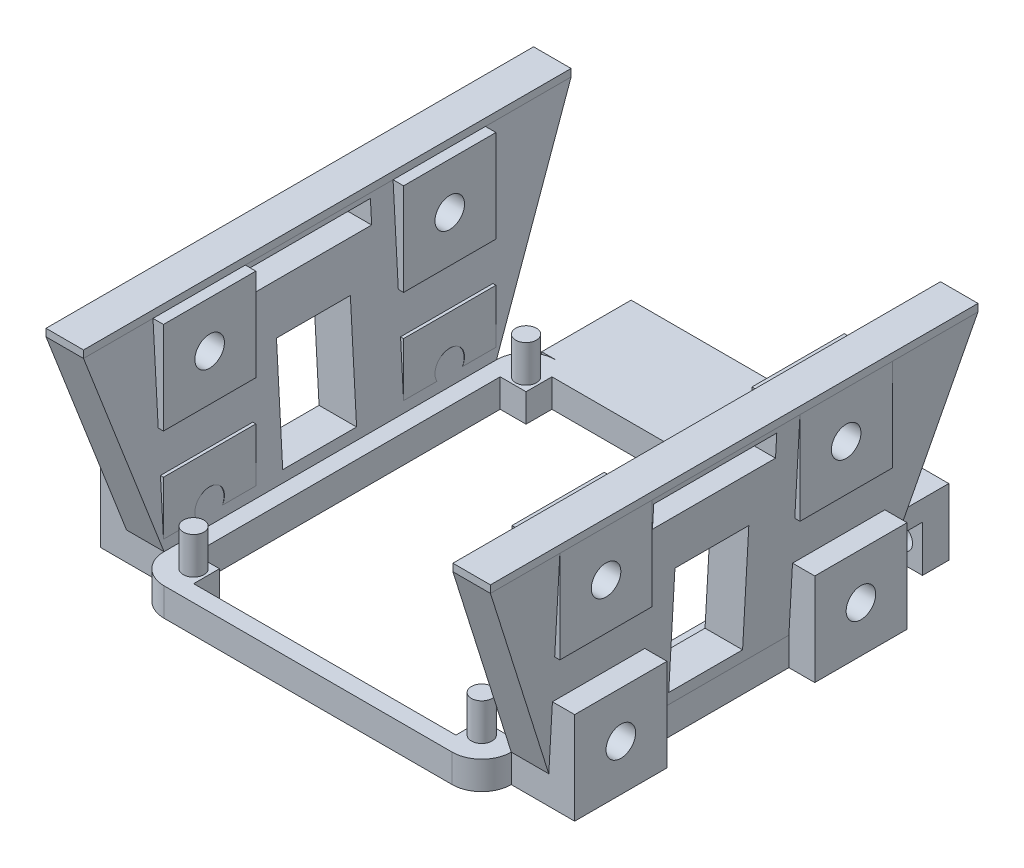
SolidWorks part; units mm, degrees
ref_plane "Front Plane" through (0, 0, 0) normal (0, 0, 1) x (1, 0, 0)
ref_plane "Top Plane" through (0, 0, 0) normal (0, 1, 0) x (1, 0, 0)
ref_plane "Right Plane" through (0, 0, 0) normal (1, 0, 0) x (0, 0, -1)
sketch "Sketch1" plane through (0, 836.5359, 0) normal (0, -1, 0) x (1, 0, 0)
  line L0 (675.181, 1276.1699) -> (675.181, 1329.1699) construction
  line L1 (655.681, 1276.1699) -> (694.6809, 1276.1699) construction
  line L2 (694.681, 1329.1699) -> (655.681, 1329.1699) construction
  line L4 (655.6809, 1276.1699) -> (694.681, 1276.1699)
  line L5 (651.6809, 1280.1699) -> (651.6809, 1325.1699)
  line L6 (655.6809, 1329.1699) -> (694.681, 1329.1699)
  line L7 (698.681, 1280.1699) -> (698.681, 1325.1699)
  line L8 (651.6809, 1276.1699) -> (698.681, 1329.1699) construction
  line L9 (651.6809, 1329.1699) -> (698.681, 1276.1699) construction
  arc A0 (651.6809, 1325.1699) -> (655.6809, 1329.1699) centre (655.6809, 1325.1699) cw
  arc A1 (655.6809, 1276.1699) -> (651.6809, 1280.1699) centre (655.6809, 1280.1699) cw
  arc A2 (694.681, 1276.1699) -> (698.681, 1280.1699) centre (694.681, 1280.1699) ccw
  arc A3 (694.681, 1329.1699) -> (698.681, 1325.1699) centre (694.681, 1325.1699) cw
  point P6 (675.181, 1302.6699)
  dimension "D3" = 4
  dimension "D1" = 53
  dimension "D2" = 47
extrude "Boss-Extrude1" add sketch "Sketch1" along normal blind 3.81
sketch "Sketch2" plane through (0, 836.5359, 0) normal (0, 1, 0) x (1, 0, 0)
  line L0 (651.6809, -1280.1699) -> (651.6809, -1325.1699) construction
  line L1 (694.6809, -1276.1699) -> (655.681, -1276.1699) construction
  line L2 (698.681, -1280.1699) -> (698.681, -1325.1699) construction
  circle A0 centre (655.6809, -1280.1699) radius 1.4
  circle A1 centre (694.6809, -1280.1699) radius 1.4
  circle A2 centre (694.681, -1325.1699) radius 1.4
  circle A3 centre (655.681, -1325.1699) radius 1.4
  dimension "D1" = 2.8
  dimension "D2" = 39
  dimension "D3" = 45
  dimension "D4" = 4
  dimension "D5" = 4
  dimension "D6" = 45
  dimension "D7" = 39
  dimension "D8" = 4
  dimension "D9" = 4
sketch "Sketch4" plane through (0, 868.1359, 0) normal (0, -1, 0) x (1, 0, 0)
  line L1 (652.181, 1336.5723) -> (698.181, 1336.5723)
  line L2 (650.181, 1334.5723) -> (650.181, 1268.5723)
  line L3 (652.181, 1266.5723) -> (698.181, 1266.5723)
  line L4 (700.181, 1334.5723) -> (700.181, 1268.5723)
  line L5 (650.181, 1336.5723) -> (700.181, 1266.5723) construction
  line L6 (650.181, 1266.5723) -> (700.181, 1336.5723) construction
  arc A0 (650.181, 1268.5723) -> (652.181, 1266.5723) centre (652.181, 1268.5723) ccw
  arc A1 (698.181, 1266.5723) -> (700.181, 1268.5723) centre (698.181, 1268.5723) ccw
  arc A2 (698.181, 1336.5723) -> (700.181, 1334.5723) centre (698.181, 1334.5723) cw
  arc A3 (652.181, 1336.5723) -> (650.181, 1334.5723) centre (652.181, 1334.5723) ccw
  point P4 (675.181, 1301.5723)
  dimension "D1" = 2
extrude "Boss-Extrude4" add sketch "Sketch4" along normal blind 5 separate body
ref_plane "Plane1" through (0, 0, 1302.6699) normal (0, 0, 1) x (1, 0, 0)
extrude "Boss-Extrude5" add sketch "Sketch2" along normal blind 5
sketch "Sketch6" plane through (0, 832.7259, 0) normal (0, -1, 0) x (1, 0, 0)
  line L0 (675.181, 1329.1699) -> (675.181, 1276.1699) construction
  line L1 (694.681, 1329.1699) -> (655.6809, 1329.1699) construction
  line L2 (655.6809, 1276.1699) -> (694.681, 1276.1699) construction
sketch "Sketch8" plane through (0, 868.1359, 0) normal (0, 1, 0) x (1, 0, 0)
  line L0 (650.181, -1268.5723) -> (650.181, -1334.5723)
  line L1 (650.181, -1268.5723) -> (645.101, -1268.5723)
  line L2 (650.181, -1334.5723) -> (645.101, -1334.5723)
  line L3 (645.101, -1268.5723) -> (645.101, -1334.5723)
  line L4 (652.181, -1266.5723) -> (698.181, -1266.5723)
  line L5 (652.181, -1266.5723) -> (652.181, -1261.4923)
  line L6 (698.181, -1266.5723) -> (698.181, -1261.4923)
  line L7 (652.181, -1261.4923) -> (698.181, -1261.4923)
  line L8 (650.181, -1301.5723) -> (700.181, -1301.5723) construction
  line L9 (700.181, -1268.5723) -> (700.181, -1334.5723) construction
  line L10 (652.181, -1341.6523) -> (698.181, -1341.6523)
  line L11 (698.181, -1336.5723) -> (698.181, -1341.6523)
  line L12 (652.181, -1336.5723) -> (652.181, -1341.6523)
  line L13 (652.181, -1336.5723) -> (698.181, -1336.5723)
  line L14 (675.181, -1329.1699) -> (675.181, -1276.1699) construction
  line L15 (705.2609, -1268.5723) -> (705.2609, -1334.5723)
  line L16 (700.1809, -1334.5723) -> (705.2609, -1334.5723)
  line L17 (700.1809, -1268.5723) -> (705.2609, -1268.5723)
  line L18 (700.1809, -1268.5723) -> (700.1809, -1334.5723)
  dimension "D1" = 5.08
extrude "Boss-Extrude7" add sketch "Sketch8" against normal up to surface (5 mm away) separate body up to face at (675.181, 863.1359, 1301.5723)
sketch "Sketch10" plane through (0, 832.7259, 0) normal (0, -1, 0) x (1, 0, 0)
  line L0 (651.6809, 1325.1699) -> (651.6809, 1280.1699)
  line L1 (651.6809, 1325.1699) -> (646.6009, 1325.1699)
  line L2 (651.6809, 1280.1699) -> (646.6009, 1280.1699)
  line L3 (646.6009, 1325.1699) -> (646.6009, 1280.1699)
  line L8 (698.681, 1325.1699) -> (698.681, 1280.1699)
  line L9 (698.681, 1325.1699) -> (703.761, 1325.1699)
  line L10 (698.681, 1280.1699) -> (703.761, 1280.1699)
  line L11 (703.761, 1325.1699) -> (703.761, 1280.1699)
  dimension "D1" = 5.08
extrude "Boss-Extrude8" add sketch "Sketch10" against normal up to surface (3.81 mm away) separate body up to face at (654.281, 836.5359, 1325.1699)
loft "Loft6" add section face at (649.1409, 836.5359, 1302.6699) section face at (647.641, 863.1359, 1301.5723) connector at (646.6009, 836.5359, 1325.1699) connector at (645.101, 863.1359, 1334.5723)
loft "Loft8" add section face at (702.7209, 863.1359, 1301.5723) section face at (701.221, 836.5359, 1302.6699) start constraint default connector at (700.1809, 863.1359, 1334.5723) connector at (698.681, 836.5359, 1325.1699)
sketch "Sketch12" plane through (0, 0, 1341.6523) normal (0, 0, 1) x (1, 0, 0)
  line L1 (645.101, 868.1359) -> (705.2609, 868.1359)
  line L2 (645.101, 868.1359) -> (645.101, 863.1359)
  line L3 (645.101, 863.1359) -> (705.2609, 863.1359)
  line L4 (705.2609, 868.1359) -> (705.2609, 863.1359)
  line L5 (645.101, 868.1359) -> (705.2609, 863.1359) construction
  line L6 (645.101, 863.1359) -> (705.2609, 868.1359) construction
  point P4 (675.181, 865.6359)
extrude "Cut-Extrude1" cut sketch "Sketch12" against normal through all
sketch "Sketch13" plane through (0, 836.5359, 0) normal (0, 1, 0) x (1, 0, 0)
  line L0 (675.181, -1329.1699) -> (675.181, -1276.1699) construction
  line L1 (657.431, -1326.9199) -> (692.931, -1326.9199)
  line L2 (653.931, -1323.4199) -> (653.931, -1281.9199)
  line L3 (657.431, -1278.4199) -> (692.931, -1278.4199)
  line L4 (696.431, -1323.4199) -> (696.431, -1281.9199)
  line L5 (653.931, -1326.9199) -> (696.431, -1278.4199) construction
  line L6 (653.931, -1278.4199) -> (696.431, -1326.9199) construction
  line L7 (675.181, -1278.4199) -> (675.181, -1326.9199) construction
  line L10 (653.931, -1281.9199) -> (657.431, -1281.9199)
  line L11 (657.431, -1278.4199) -> (657.431, -1281.9199)
  line L12 (653.931, -1278.4199) -> (657.431, -1281.9199) construction
  line L13 (653.931, -1281.9199) -> (657.431, -1278.4199) construction
  line L14 (-2.0955, -1302.6699) -> (2.0955, -1302.6699) construction
  line L15 (653.931, -1323.4199) -> (657.431, -1326.9199) construction
  line L16 (653.931, -1326.9199) -> (657.431, -1323.4199) construction
  line L17 (657.431, -1326.9199) -> (657.431, -1323.4199)
  line L18 (653.931, -1323.4199) -> (657.431, -1323.4199)
  line L21 (696.431, -1326.9199) -> (692.931, -1323.4199) construction
  line L22 (696.431, -1323.4199) -> (692.931, -1326.9199) construction
  line L25 (696.431, -1323.4199) -> (692.931, -1323.4199)
  line L26 (692.931, -1326.9199) -> (692.931, -1323.4199)
  line L27 (696.431, -1281.9199) -> (692.931, -1278.4199) construction
  line L28 (696.431, -1278.4199) -> (692.931, -1281.9199) construction
  line L29 (692.931, -1278.4199) -> (692.931, -1281.9199)
  line L30 (696.431, -1281.9199) -> (692.931, -1281.9199)
  point P0 (675.181, -1302.6699)
  point P10 (655.681, -1280.1699)
  point P18 (655.681, -1325.1699)
  point P22 (694.681, -1325.1699)
  point P26 (694.681, -1280.1699)
  dimension "D1" = 48.5
  dimension "D2" = 42.5
  dimension "D3" = 3.5
  dimension "D4" = 3.5
extrude "Cut-Extrude2" cut sketch "Sketch13" against normal through all
ref_plane "Plane2" through (675.181, 0, 0) normal (1, 0, 0) x (0, 0, -1)
sketch "Sketch14" plane through (675.181, 0, 0) normal (1, 0, 0) x (0, 0, -1)
  line L0 (-1304.1057, 838.1559) -> (-1304.1057, 853.1559) construction
  line L1 (-1304.1057, 853.1559) -> (-1304.1057, 863.1359) construction
  line L2 (-1309.0256, 838.0359) -> (-1299.0256, 838.0359)
  line L3 (-1309.0256, 838.0359) -> (-1309.0256, 853.0359)
  line L4 (-1309.0256, 853.0359) -> (-1299.0256, 853.0359)
  line L5 (-1299.0256, 838.0359) -> (-1299.0256, 853.0359)
  line L6 (-1309.0256, 838.0359) -> (-1299.0256, 853.0359) construction
  line L7 (-1309.0256, 853.0359) -> (-1299.0256, 838.0359) construction
  line L8 (-1325.1699, 836.5359) -> (-1280.1699, 836.5359) construction
  line L9 (-1325.1699, 836.5359) -> (-1325.1699, 832.7259) construction
  line L10 (-1325.1699, 832.7259) -> (-1280.1699, 832.7259) construction
  line L11 (-1280.1699, 836.5359) -> (-1280.1699, 832.7259) construction
  line L12 (-1325.1699, 836.5359) -> (-1280.1699, 832.7259) construction
  line L13 (-1325.1699, 832.7259) -> (-1280.1699, 836.5359) construction
  line L18 (-1295.7772, 859.486) -> (-1312.4342, 859.486)
  line L19 (-1295.7772, 859.486) -> (-1295.7772, 862.5199)
  line L20 (-1312.4342, 859.486) -> (-1312.4342, 862.5199)
  line L21 (-1295.7772, 862.5199) -> (-1312.4342, 862.5199)
  line L22 (-1295.7772, 859.486) -> (-1312.4342, 862.5199) construction
  line L23 (-1312.4342, 859.486) -> (-1295.7772, 862.5199) construction
  point P2 (-1304.0256, 845.5359)
  point P11 (-1302.6699, 834.6309)
  point P16 (-1304.1057, 861.003)
  dimension "D2" = 15
  dimension "D3" = 10
  dimension "D4" = 1.5
extrude "Cut-Extrude3" cut sketch "Sketch14" against normal through all both and the other way through all
sketch "Sketch15" plane through (0, 863.1359, 0) normal (0, 1, 0) x (1, 0, 0)
  line L0 (650.181, -1268.5723) -> (645.101, -1268.5723) construction
  line L1 (645.101, -1268.5723) -> (645.101, -1334.5723) construction
  line L2 (705.2609, -1334.5723) -> (705.2609, -1268.5723) construction
  line L3 (700.181, -1334.5723) -> (705.2609, -1334.5723) construction
  circle A0 centre (647.641, -1272.5723) radius 2
  circle A1 centre (702.7209, -1272.5723) radius 2
  circle A2 centre (702.7209, -1330.5723) radius 2
  circle A3 centre (647.641, -1330.5723) radius 2
  dimension "D1" = 4
  dimension "D2" = 4
  dimension "D3" = 2.54
  dimension "D4" = 2.54
  dimension "D5" = 4
sketch "Sketch16" plane through (646.6009, 0, 0) normal (-1, 0, 0) x (0, 0, 1)
  line L0 (1302.6699, 832.7259) -> (1302.6699, 855.8005) construction
  line L1 (1325.1699, 832.7259) -> (1280.1699, 832.7259) construction
  line L2 (1325.1699, 845.2259) -> (1312.6699, 832.7259) construction
  line L3 (1280.1699, 832.7259) -> (1292.6699, 832.7259)
  line L4 (1280.1699, 832.7259) -> (1280.1699, 845.2259)
  line L5 (1280.1699, 845.2259) -> (1292.6699, 845.2259)
  line L6 (1292.6699, 832.7259) -> (1292.6699, 845.2259)
  line L7 (1280.1699, 832.7259) -> (1292.6699, 845.2259) construction
  line L8 (1280.1699, 845.2259) -> (1292.6699, 832.7259) construction
  line L9 (1325.1699, 832.7259) -> (1312.6699, 845.2259) construction
  line L10 (1312.6699, 832.7259) -> (1312.6699, 845.2259)
  line L11 (1325.1699, 845.2259) -> (1312.6699, 845.2259)
  line L12 (1325.1699, 832.7259) -> (1325.1699, 845.2259)
  line L13 (1325.1699, 832.7259) -> (1312.6699, 832.7259)
  line L14 (1280.1699, 845.2259) -> (1280.1699, 863.1359) construction
  line L15 (1268.5723, 863.1359) -> (1334.5723, 863.1359) construction
  line L16 (1312.6699, 845.2259) -> (1312.6699, 863.1359) construction
  line L17 (1280.1699, 863.1359) -> (1292.6699, 863.1359)
  line L18 (1280.1699, 863.1359) -> (1280.1699, 850.6359)
  line L19 (1280.1699, 850.6359) -> (1292.6699, 850.6359)
  line L20 (1292.6699, 863.1359) -> (1292.6699, 850.6359)
  line L21 (1280.1699, 863.1359) -> (1292.6699, 850.6359) construction
  line L22 (1280.1699, 850.6359) -> (1292.6699, 863.1359) construction
  line L24 (1312.6699, 863.1359) -> (1325.1699, 863.1359)
  line L25 (1312.6699, 863.1359) -> (1312.6699, 850.6359)
  line L26 (1312.6699, 850.6359) -> (1325.1699, 850.6359)
  line L27 (1325.1699, 863.1359) -> (1325.1699, 850.6359)
  line L28 (1312.6699, 863.1359) -> (1325.1699, 850.6359) construction
  line L29 (1312.6699, 850.6359) -> (1325.1699, 863.1359) construction
  circle A0 centre (1286.4199, 838.9759) radius 2
  circle A1 centre (1318.9199, 838.9759) radius 2
  circle A2 centre (1286.4199, 856.8859) radius 1.6
  circle A3 centre (1318.9199, 856.8859) radius 1.6
  point P8 (1286.4199, 838.9759)
  point P14 (1318.9199, 838.9759)
  point P25 (1286.4199, 856.8859)
  point P32 (1318.9199, 856.8859)
  dimension "D3" = 4
  dimension "D4" = 4
  dimension "D7" = 3.2
  dimension "D1" = 12.5
  dimension "D2" = 12.5
  dimension "D5" = 12.5
  dimension "D6" = 12.5
extrude "Boss-Extrude10" add sketch "Sketch16" along normal blind 1.5 and the other way blind 5
extrude "Boss-Extrude11" add sketch "Sketch16<2>" against normal blind 1.5 and the other way blind 5 from surface starting at face at (703.761, 835.5834, 1297.0449)
sketch "Sketch16<2>" plane through (646.6009, 0, 0) normal (-1, 0, 0) x (0, 0, 1) same geometry as "Sketch16"
sketch "Sketch17" plane through (0, 863.1359, 0) normal (0, 1, 0) x (1, 0, 0)
  line L1 (645.101, -1268.5723) -> (650.181, -1268.5723)
  line L2 (645.101, -1268.5723) -> (645.101, -1334.5723)
  line L3 (645.101, -1334.5723) -> (650.181, -1334.5723)
  line L4 (650.181, -1268.5723) -> (650.181, -1334.5723)
  line L5 (645.101, -1268.5723) -> (650.181, -1334.5723) construction
  line L6 (645.101, -1334.5723) -> (650.181, -1268.5723) construction
  line L7 (700.1809, -1268.5723) -> (705.2609, -1268.5723)
  line L8 (700.1809, -1268.5723) -> (700.1809, -1334.5723)
  line L9 (700.1809, -1334.5723) -> (705.2609, -1334.5723)
  line L10 (705.2609, -1268.5723) -> (705.2609, -1334.5723)
  line L11 (700.1809, -1268.5723) -> (705.2609, -1334.5723) construction
  line L12 (700.1809, -1334.5723) -> (705.2609, -1268.5723) construction
  point P4 (647.641, -1301.5723)
  point P11 (702.7209, -1301.5723)
sketch "Sketch19" plane through (645.1009, 0, 0) normal (-1, 0, 0) x (0, 0, 1)
  circle A0 centre (1286.4199, 856.8859) radius 2
  circle A1 centre (1318.9199, 856.8859) radius 2
  dimension "D1" = 4
extrude "Cut-Extrude4" cut sketch "Sketch19" against normal through all
extrude "Boss-Extrude13" add sketch "Sketch17" along normal blind 1
sketch "Sketch23" plane through (0, 0, 1276.1699) normal (0, 0, -1) x (-1, 0, 0)
  line L0 (-686.8023, 827.5359) -> (-696.8023, 827.5359)
  line L1 (-675.3023, 836.5359) -> (-675.3023, 818.5384) construction
  line L2 (-655.6809, 836.5359) -> (-694.681, 836.5359) construction
  line L3 (-696.8023, 827.5359) -> (-696.8023, 836.5359)
  line L4 (-696.8023, 836.5359) -> (-653.8023, 836.5359)
  line L5 (-686.8023, 827.5359) -> (-683.3023, 831.707)
  line L6 (-683.3023, 831.707) -> (-667.3023, 831.707)
  line L7 (-663.8023, 827.5359) -> (-667.3023, 831.707)
  line L8 (-698.681, 836.5359) -> (-698.681, 832.7259) construction
  line L9 (-653.8023, 827.5359) -> (-653.8023, 836.5359)
  line L10 (-663.8023, 827.5359) -> (-653.8023, 827.5359)
  point P3 (-675.3023, 831.707)
  dimension "D1" = 21.5
  dimension "D2" = 23.3787
  dimension "D3" = 9
  dimension "D4" = 10
  dimension "D5" = 8
  dimension "D6" = 50
extrude "Boss-Extrude14" add sketch "Sketch23" along normal blind 12.1
sketch "Sketch24" plane through (0, 0, 1264.0699) normal (0, 0, -1) x (-1, 0, 0)
  circle A0 centre (-693.8809, 830.6109) radius 1.575
  circle A1 centre (-656.4809, 830.6109) radius 1.575
  dimension "D1" = 3.15
extrude "Cut-Extrude5" cut sketch "Sketch24" against normal up to next
sketch "Sketch25" plane through (696.8023, 0, 0) normal (1, 0, 0) x (0, 0, -1)
  line L0 (-1276.1699, 827.5359) -> (-1276.1699, 832.7259)
  line L1 (-1276.1699, 827.5359) -> (-1270.1699, 827.5359)
  line L2 (-1276.1699, 832.7259) -> (-1270.1699, 832.7259)
  line L3 (-1270.1699, 827.5359) -> (-1270.1699, 832.7259)
  dimension "D1" = 6
extrude "Cut-Extrude6" cut sketch "Sketch25" against normal through all
sketch "Sketch26" plane through (0, 0, 1270.1699) normal (0, 0, 1) x (1, 0, 0)
  line L1 (653.8023, 827.5359) -> (660.0523, 827.5359)
  line L2 (653.8023, 827.5359) -> (653.8023, 833.7859)
  line L3 (653.8023, 833.7859) -> (660.0523, 833.7859)
  line L4 (660.0523, 827.5359) -> (660.0523, 833.7859)
  line L5 (653.8023, 827.5359) -> (660.0523, 833.7859) construction
  line L6 (653.8023, 833.7859) -> (660.0523, 827.5359) construction
  line L7 (696.8023, 827.5359) -> (690.5523, 827.5359)
  line L8 (696.8023, 827.5359) -> (696.8023, 833.7859)
  line L9 (696.8023, 833.7859) -> (690.5523, 833.7859)
  line L10 (690.5523, 827.5359) -> (690.5523, 833.7859)
  line L11 (696.8023, 827.5359) -> (690.5523, 833.7859) construction
  line L12 (696.8023, 833.7859) -> (690.5523, 827.5359) construction
  point P4 (656.9273, 830.6609)
  point P10 (693.6773, 830.6609)
  dimension "D1" = 6.25
  dimension "D2" = 6.25
extrude "Cut-Extrude8" cut sketch "Sketch26" against normal blind 2.54 and the other way blind 1
sketch "Sketch27" plane through (705.261, 0, 0) normal (1, 0, 0) x (0, 0, -1)
  line L1 (-1325.1699, 845.2259) -> (-1312.6699, 845.2259)
  line L2 (-1325.1699, 845.2259) -> (-1325.1699, 832.7259)
  line L3 (-1325.1699, 832.7259) -> (-1312.6699, 832.7259)
  line L4 (-1312.6699, 845.2259) -> (-1312.6699, 832.7259)
  line L5 (-1325.1699, 845.2259) -> (-1312.6699, 832.7259) construction
  line L6 (-1325.1699, 832.7259) -> (-1312.6699, 845.2259) construction
  line L7 (-1292.6699, 845.2259) -> (-1280.1699, 845.2259)
  line L8 (-1292.6699, 845.2259) -> (-1292.6699, 832.7259)
  line L9 (-1292.6699, 832.7259) -> (-1280.1699, 832.7259)
  line L10 (-1280.1699, 845.2259) -> (-1280.1699, 832.7259)
  line L11 (-1292.6699, 845.2259) -> (-1280.1699, 832.7259) construction
  line L12 (-1292.6699, 832.7259) -> (-1280.1699, 845.2259) construction
  circle A0 centre (-1318.9199, 838.9759) radius 2
  circle A1 centre (-1286.4199, 838.9759) radius 2
  dimension "D1" = 4
extrude "Boss-Extrude15" add sketch "Sketch27" along normal blind 2
extrude "Boss-Extrude16" add sketch "Sketch27<2>" against normal blind 2 from surface starting at face at (645.1009, 838.9759, 1286.4199)
sketch "Sketch27<2>" plane through (705.261, 0, 0) normal (1, 0, 0) x (0, 0, -1) same geometry as "Sketch27"
